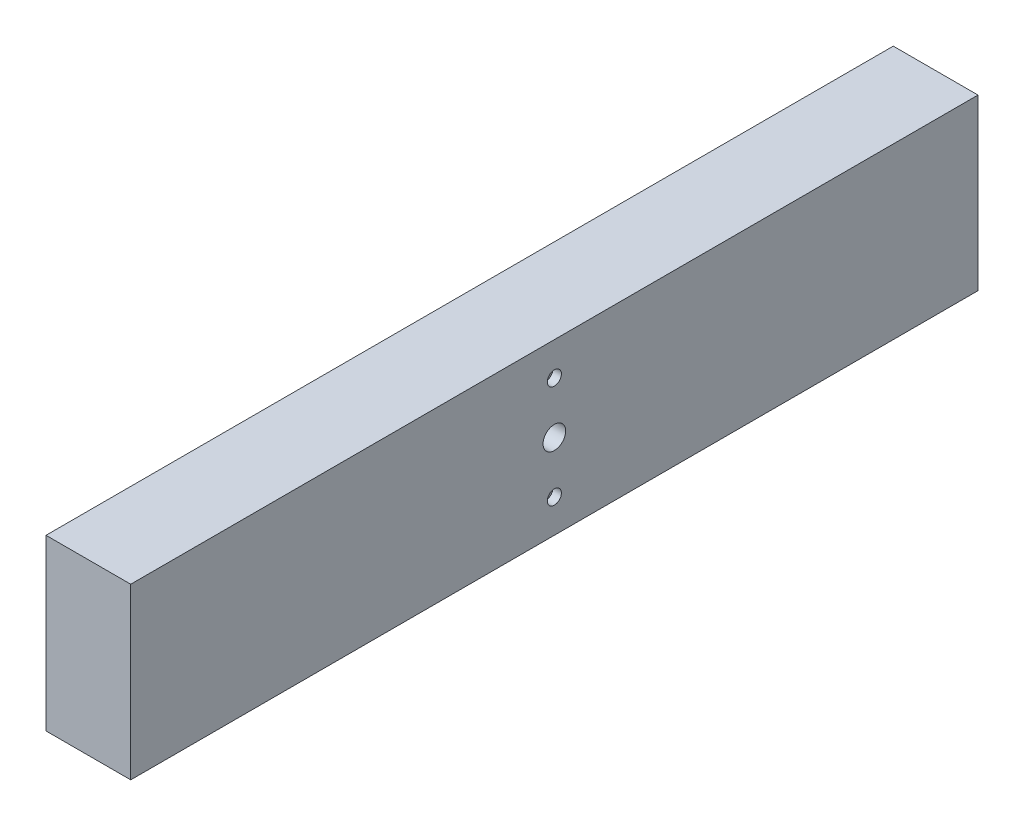
SolidWorks part; units mm, degrees
ref_plane "Front Plane" through (0, 0, 0) normal (0, 0, 1) x (1, 0, 0)
ref_plane "Top Plane" through (0, 0, 0) normal (0, 1, 0) x (1, 0, 0)
ref_plane "Right Plane" through (0, 0, 0) normal (1, 0, 0) x (0, 0, -1)
sketch "Sketch1" plane through (0, 0, 0) normal (0, 0, 1) x (1, 0, 0)
  line L1 (-15, -30) -> (15, -30)
  line L2 (-15, -30) -> (-15, 30)
  line L3 (-15, 30) -> (15, 30)
  line L4 (15, -30) -> (15, 30)
  line L5 (-15, -30) -> (15, 30) construction
  line L6 (-15, 30) -> (15, -30) construction
  point P0 (0, 0)
  dimension "D1" = 60
  dimension "D2" = 30
extrude "Boss-Extrude1" add sketch "Sketch1" along normal blind 150 and the other way blind 150
sketch "Sketch2" plane through (15, 0, 0) normal (1, 0, 0) x (0, 0, -1)
  line L0 (-150, 0) -> (150, 0) construction
  line L1 (-150, -30) -> (-150, 30) construction
  line L2 (150, -30) -> (150, 30) construction
  line L3 (0, 30) -> (0, -30) construction
  line L4 (-150, 30) -> (150, 30) construction
  line L5 (-150, -30) -> (150, -30) construction
  circle A0 centre (0, 18.25) radius 2.5
  circle A1 centre (0, -18.25) radius 2.5
  dimension "D1" = 5
  dimension "D3" = 36.5
extrude "Cut-Extrude1" cut sketch "Sketch2" against normal blind 3
sketch "Sketch3" plane through (15, 0, 0) normal (1, 0, 0) x (0, 0, -1)
  line L0 (0, 30) -> (0, -30) construction
  line L1 (-150, 30) -> (150, 30) construction
  line L2 (-150, -30) -> (150, -30) construction
  circle A0 centre (0, 0) radius 4
  dimension "D1" = 8
extrude "Cut-Extrude2" cut sketch "Sketch3" against normal through all
